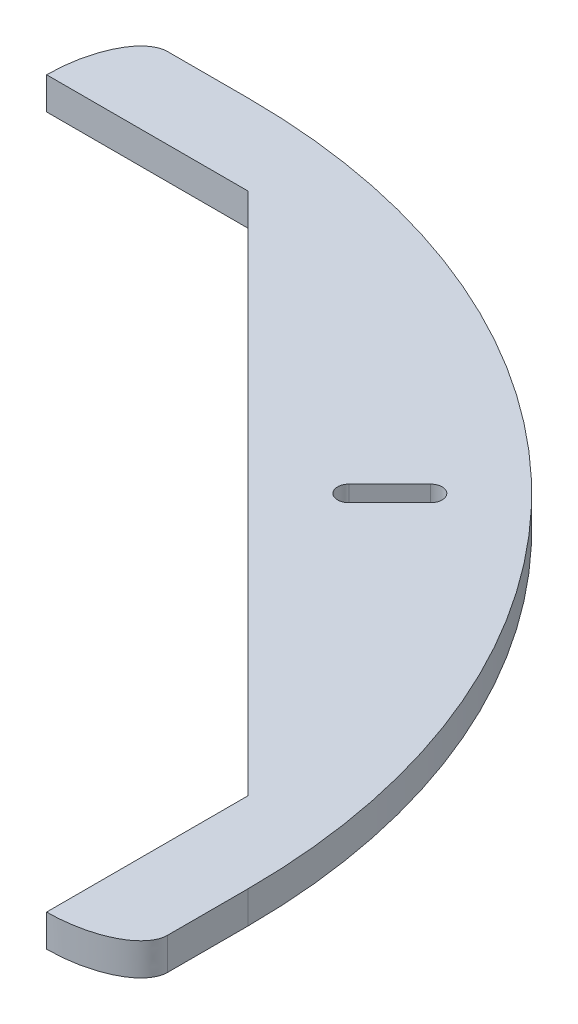
SolidWorks part; units mm, degrees
ref_plane "Front Plane" through (0, 0, 0) normal (0, 0, 1) x (1, 0, 0)
ref_plane "Top Plane" through (0, 0, 0) normal (0, 1, 0) x (1, 0, 0)
ref_plane "Right Plane" through (0, 0, 0) normal (1, 0, 0) x (0, 0, -1)
sketch "Sketch1" plane through (0, 0, 0) normal (0, 1, 0) x (1, 0, 0)
  line L1 (0, 120.65) -> (12.7, 120.65)
  line L3 (120.65, 0) -> (120.65, 12.7)
  line L4 (0, 107.95) -> (25.4, 107.95)
  line L5 (25.4, 107.95) -> (107.95, 25.4)
  line L6 (107.95, 25.4) -> (107.95, 0)
  line L7 (0, 0) -> (0, 107.95) construction
  line L8 (0, 107.95) -> (0, 120.65)
  line L9 (0, 0) -> (107.95, 0) construction
  line L10 (107.95, 0) -> (120.65, 0)
  line L12 (74.6363, 74.6363) -> (66.675, 66.675) construction
  line L13 (74.6363, 74.6363) -> (81.0709, 81.0709) construction
  line L14 (73.3635, 75.909) -> (79.7981, 82.3437)
  line L15 (75.909, 73.3635) -> (82.3437, 79.7981)
  line L16 (81.0709, 81.0709) -> (89.0322, 89.0322) construction
  arc A0 (12.7, 120.65) -> (120.65, 12.7) centre (12.7, 12.7) cw
  arc A1 (73.3635, 75.909) -> (75.909, 73.3635) centre (74.6363, 74.6363) ccw
  arc A2 (82.3437, 79.7981) -> (79.7981, 82.3437) centre (81.0709, 81.0709) ccw
  point P15 (77.8536, 77.8536)
  point P20 (73.3635, 73.3635)
  point P21 (82.3437, 82.3437)
  point P23 (79.1264, 76.5808)
  dimension "D5" = 12.7
  dimension "D1" = 25.4
  dimension "D2" = 120.65
  dimension "D3" = 12.7
  dimension "D4" = 12.7
  dimension "D6" = 3.6
extrude "Boss-Extrude1" add sketch "Sketch1" along normal blind 5.08
sketch "Sketch2" plane through (0, 0, 0) normal (-1, 0, 0) x (0, 0, 1)
  line L4 (-120.65, 0) -> (-107.95, 0)
  line L5 (-107.95, 0) -> (-107.95, 5.08)
  line L6 (-107.95, 5.08) -> (-120.65, 5.08)
  line L7 (-120.65, 5.08) -> (-120.65, 0)
  line L8 (-120.65, 0) -> (-107.95, 0)
  line L9 (-107.95, 0) -> (-107.95, 5.08)
  line L10 (-107.95, 5.08) -> (-120.65, 5.08)
  line L11 (-120.65, 5.08) -> (-120.65, 0)
  dimension "D1" = 0
extrude "Boss-Extrude2" add sketch "Sketch2" along normal blind 6.35
ref_plane "Plane1" through (0, 0, 0) normal (0.7071, 0, 0.7071) x (0.7071, 0, -0.7071)
mirror "Mirror2" about plane through (0, 0, 0) normal (0.7071, 0, 0.7071) of "Boss-Extrude2"
fillet "Fillet3" radius 6.35 1 edges at (-6.35, 2.54, -120.65) second distance 12.7 first distance on face at (3.175, 2.54, -120.65)
fillet "Fillet4" radius 6.35 1 edges at (120.65, 2.54, 6.35) second distance 12.7 first distance on face at (120.65, 2.54, -3.175)
equation "\"Foamcore\"= 0.2in"
equation "\"MDF\"= 0.2in"
equation "\"D1@Boss-Extrude1\"=\"MDF\""
